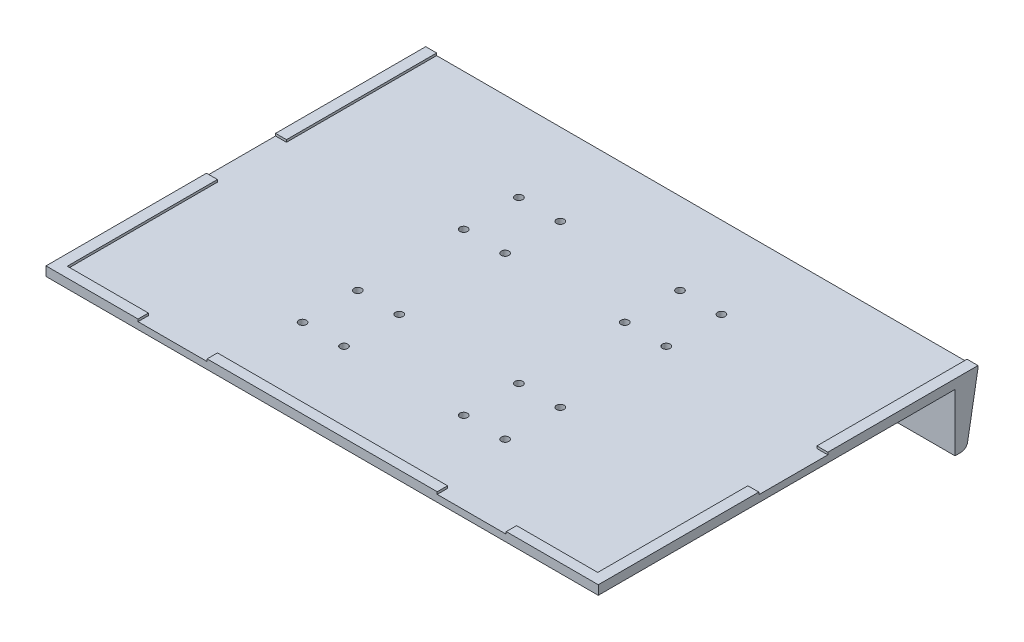
SolidWorks part; units mm, degrees
ref_plane "Front Plane" through (0, 0, 0) normal (0, 0, 1) x (1, 0, 0)
ref_plane "Top Plane" through (0, 0, 0) normal (0, 1, 0) x (1, 0, 0)
ref_plane "Right Plane" through (0, 0, 0) normal (1, 0, 0) x (0, 0, -1)
sketch "Sketch2" plane through (0, 0, 0) normal (0, 1, 0) x (1, 0, 0)
  line L0 (80, -78) -> (50, -78)
  line L1 (-120, 82.5) -> (120, 82.5)
  line L2 (-120, 82.5) -> (-120, -82.5)
  line L3 (-120, -82.5) -> (120, -82.5)
  line L4 (120, 82.5) -> (120, -82.5)
  line L5 (0, -82.5) -> (0, 82.5) construction
  line L6 (-120, 0) -> (120, 0) construction
  line L7 (-115.25, 82.5) -> (115.25, 82.5)
  line L8 (-115.25, 82.5) -> (-115.25, -78)
  line L9 (-115.25, -78) -> (115.25, -78)
  line L10 (115.25, 82.5) -> (115.25, -78)
  line L11 (0, -78) -> (0, 82.5) construction
  line L12 (-115.25, 2.25) -> (115.25, 2.25) construction
  line L13 (-80, -82.5) -> (-50, -82.5)
  line L14 (-80, -82.5) -> (-80, -78)
  line L15 (-80, -78) -> (-50, -78)
  line L16 (-50, -82.5) -> (-50, -78)
  line L17 (-65, -78) -> (-65, -82.5) construction
  line L18 (-80, -80.25) -> (-50, -80.25) construction
  line L19 (50, -82.5) -> (50, -78)
  line L20 (80, -82.5) -> (50, -82.5)
  line L21 (80, -82.5) -> (80, -78)
  line L22 (120, -12.75) -> (115.25, -12.75)
  line L23 (-120, 17.25) -> (-115.25, 17.25)
  line L24 (-120, 17.25) -> (-120, -12.75)
  line L25 (-120, -12.75) -> (-115.25, -12.75)
  line L26 (-115.25, 17.25) -> (-115.25, -12.75)
  line L27 (-117.625, -12.75) -> (-117.625, 17.25) construction
  line L28 (-120, 2.25) -> (-115.25, 2.25) construction
  line L29 (115.25, 17.25) -> (115.25, -12.75)
  line L30 (120, 17.25) -> (115.25, 17.25)
  line L31 (120, 17.25) -> (120, -12.75)
  line L33 (-35, 35) -> (35, 35) construction
  line L34 (-35, 35) -> (-35, -35) construction
  line L35 (-35, -35) -> (35, -35) construction
  line L36 (35, 35) -> (35, -35) construction
  line L37 (0, -35) -> (0, 35) construction
  line L38 (-35, 0) -> (35, 0) construction
  line L39 (-44, 47) -> (-26, 47) construction
  line L40 (-44, 47) -> (-44, 23) construction
  line L41 (-44, 23) -> (-26, 23) construction
  line L42 (-26, 47) -> (-26, 23) construction
  line L43 (-35, 23) -> (-35, 47) construction
  line L44 (-44, 35) -> (-26, 35) construction
  circle A0 centre (-44, 47) radius 1.65
  circle A1 centre (-26, 47) radius 1.65
  circle A2 centre (-26, 23) radius 1.65
  circle A3 centre (-44, 23) radius 1.65
  circle A4 centre (26, 47) radius 1.65
  circle A5 centre (44, 47) radius 1.65
  circle A6 centre (26, 23) radius 1.65
  circle A7 centre (44, 23) radius 1.65
  circle A8 centre (26, -23) radius 1.65
  circle A9 centre (44, -23) radius 1.65
  circle A10 centre (26, -47) radius 1.65
  circle A11 centre (44, -47) radius 1.65
  circle A12 centre (-44, -23) radius 1.65
  circle A13 centre (-26, -23) radius 1.65
  circle A14 centre (-44, -47) radius 1.65
  circle A15 centre (-26, -47) radius 1.65
  point P0 (0, 0)
  point P24 (0, 0)
  point P35 (0, 0)
  point P178 (0, 2.25)
  point P226 (-65, -80.25)
  point P315 (-117.625, 2.25)
  dimension "D13" = 3.3
  dimension "D1" = 165
  dimension "D2" = 240
  dimension "D3" = 160.5
  dimension "D4" = 230.5
  dimension "D5" = 30
  dimension "D6" = 50
  dimension "D7" = 160.5
  dimension "D8" = 30
  dimension "D9" = 70
  dimension "D10" = 70
  dimension "D11" = 24
  dimension "D12" = 18
  dimension "D16" = 70
  dimension "D17" = 70
  dimension "D14" = 2
  dimension "D15" = 2
extrude "Boss-Extrude3" add sketch "Sketch2" along normal blind 4 contours L2 L23 L8 L1 | L25 L2 L3 L14 L9 L8 | L3 L19 L9 L16 | L4 L22 L10 L9 L21 L3 | L30 L4 L1 L10 region at (97.625, 0, 78.8041) region at (0, 0, 80.25) region at (-80.8041, 0, 80.25) region at (117.625, 0, -49.875) region at (-117.625, 0, -49.875)
extrude "Boss-Extrude4" add sketch "Sketch2<5>" along normal blind 3 contours L10 L1 L8 L9 L0 A15 A14 A13 A12 A11 A10 A9 A8 A7 A6 A5 A4 A3 A2 A1 A0 | L2 L25 L8 L23 | L3 L16 L9 L14 | L3 L21 L0 L19 | L4 L30 L10 L22 region at (65, 0, 80.25) region at (0, 0, -2.2584) region at (-65, 0, 80.25) region at (117.625, 0, -2.25) region at (-117.625, 0, -2.25)
sketch "Sketch2<5>" plane through (0, 0, 0) normal (0, 1, 0) x (1, 0, 0) same geometry as "Sketch2"
sketch "Sketch3" plane through (0, 0, 0) normal (0, -1, 0) x (1, 0, 0)
  line L0 (-120, -82.5) -> (-120, 82.5) construction
  line L1 (120, -82.5) -> (-120, -82.5)
  line L2 (120, -82.5) -> (120, -72.5)
  line L3 (120, -72.5) -> (-120, -72.5)
  line L4 (-120, -82.5) -> (-120, -72.5)
  line L5 (0, -72.5) -> (0, -82.5) construction
  line L6 (120, -77.5) -> (-120, -77.5) construction
  point P432 (0, -77.5)
  dimension "D1" = 10
extrude "Boss-Extrude5" add sketch "Sketch3" along normal blind 25
sketch "Sketch4" plane through (120, 0, 0) normal (1, 0, 0) x (0, 0, -1)
  line L0 (82.5, 3) -> (77.5628, -25)
  line L1 (82.5, 4) -> (82.5, -25) construction
  line L2 (82.5, -25) -> (72.5, -25) construction
  line L3 (77.5628, -25) -> (82.5, -25)
  line L4 (82.5, -25) -> (82.5, 3)
  line L5 (82.5, 4) -> (17.25, 4) construction
  dimension "D1" = 1
  dimension "D2" = 10
extrude "Cut-Extrude1" cut sketch "Sketch4" against normal through all
fillet "Fillet2" radius 3 1 edges at (0, -25, -77.5628)
